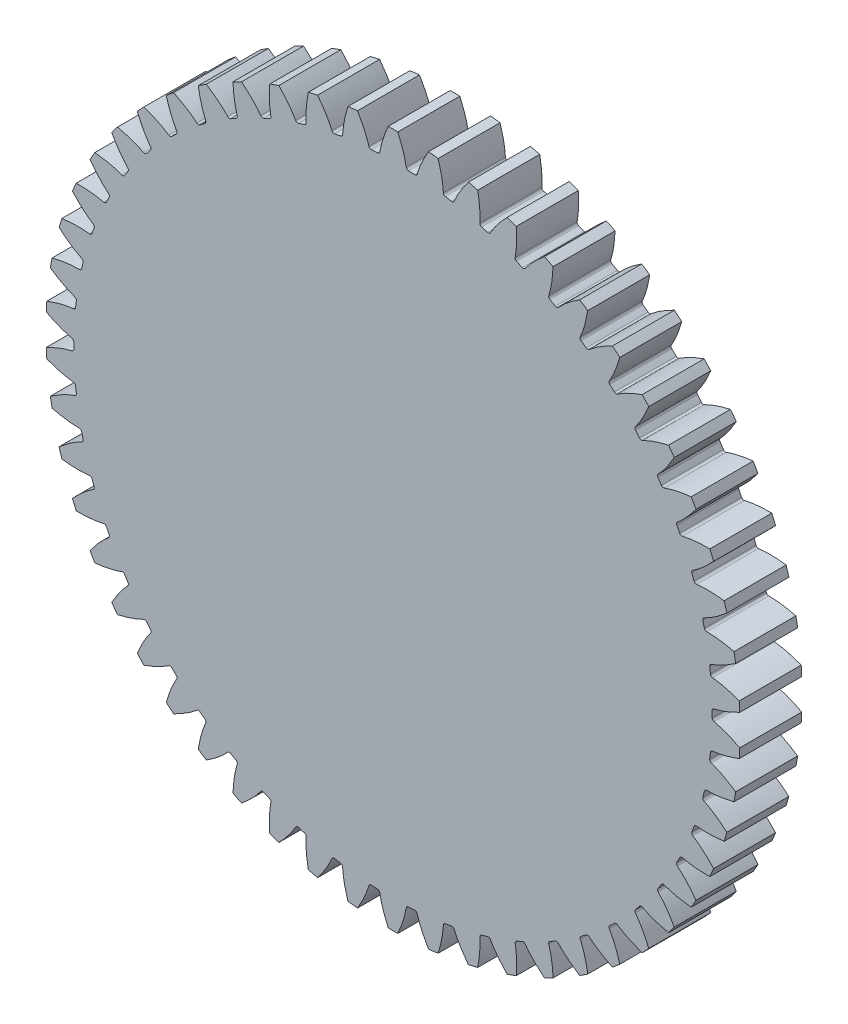
SolidWorks part; units mm, degrees
ref_plane "前视基准面" through (0, 0, 0) normal (0, 0, 1) x (1, 0, 0)
ref_plane "上视基准面" through (0, 0, 0) normal (0, 1, 0) x (1, 0, 0)
ref_plane "右视基准面" through (0, 0, 0) normal (1, 0, 0) x (0, 0, -1)
other "Configuration Table"
sketch "circles" plane through (0, 0, 0) normal (0, 0, 1) x (1, 0, 0)
  circle A0 centre (0, 0) radius 56000
  circle A1 centre (0, 0) radius 51500
  circle A2 centre (0, 0) radius 50743.4015
  circle A3 centre (0, 0) radius 54000
  dimension "D1" = 108000
  dimension "D2" = 101486.803
  dimension "D3" = 103000
  dimension "D4" = 112000
extrude "Gear_extrude" add sketch "circles" along normal blind 10000 contours A0
sketch "Involute" plane through (0, 0, 10000) normal (0, 0, 1) x (1, 0, 0)
  spline S0 degree 4 poles (50738.2969, -719.7424) (50738.6989, -719.7492) (50739.5031, -719.764) (50741.1112, -719.7997) (50743.5232, -719.8655) (50746.3369, -719.9491) (50750.356, -720.0854) (50755.1783, -720.2676) (50762.4104, -720.5706) (50772.0509, -721.0292) (50783.2948, -721.6297) (50796.1407, -722.393) (50812.1927, -723.4317) (50831.1111, -724.7774) (50852.8918, -726.4774) (50877.5298, -728.5801) (50901.8186, -730.8112) (50936.9721, -734.252) (50982.9627, -739.1667) (51043.9608, -746.3579) (51109.3546, -754.947) (51168.3219, -763.3206) (51234.9474, -773.3569) (51305.0207, -784.5405) (51393.4421, -799.6216) (51500.0905, -819.2298) (51613.1581, -841.4974) (51750.5558, -870.3767) (51876.7746, -898.8424) (52009.7781, -930.5506) (52182.9235, -974.0637) (52384.1424, -1027.6994) (52660.7454, -1107.2667) (52993.7639, -1211.7024) (53347.3188, -1331.9713) (53715.0055, -1466.8362) (54079.5977, -1609.7914) (54441.1235, -1760.3096) (54840.8093, -1936.0605) (55280.9542, -2141.1202) (55760.0369, -2378.2031) (56276.3509, -2650.0079) (56789.448, -2936.035) (57295.8631, -3233.7171) (57795.6354, -3542.4178) (58288.7943, -3861.5657) (58775.374, -4190.6497) (59255.4093, -4529.2084) (59728.9284, -4876.8157) (60195.9642, -5233.0852) (60656.5448, -5597.6556) (61110.7025, -5970.1966) (61558.4641, -6350.3958) (61999.8643, -6737.9683) (62434.9248, -7132.6363) (62863.6782, -7534.1477) (63286.1505, -7942.2588) (63702.3713, -8356.7431) (64112.3686, -8777.3843) (64516.1704, -9203.9774) (64916.8337, -9639.6208) (65409.1026, -10190.4255) (65986.8423, -10861.6333) (66642.4849, -11659.2604) (67364.4576, -12586.1414) (68062.5571, -13531.1238) (68736.9923, -14493.1316) (69387.9685, -15471.1592) (70015.6898, -16464.2658) (70620.3586, -17471.568) (71202.1764, -18492.2354) (71761.342, -19525.4818) (72298.0542, -20570.566) (72812.5079, -21626.7804) (73304.8974, -22693.4532) (73775.4183, -23769.9508) (74224.2605, -24855.659) (74651.6166, -25950.0005) (75057.677, -27052.4209) (75442.6292, -28162.3848) (75806.6612, -29279.3834) (76149.9593, -30402.927) (76472.7078, -31532.5421) (76775.0908, -32667.7749) (77057.2917, -33808.1917) (77319.492, -34953.3709) (77561.8726, -36102.9072) (77784.6129, -37256.408) (77987.8917, -38413.4962) (78171.8865, -39573.8054) (78336.7738, -40736.9815) (78482.7294, -41902.6839) (78625.8276, -43216.5679) (78757.7244, -44679.1708) (78869.1367, -46290.7564) (78936.4624, -47757.7842) (78969.4904, -48932.1208) (78982.0634, -49739.6722) (78985.8285, -50143.4774) (78987.2877, -50437.1606) (78987.6982, -50602.3592) (78987.801, -50712.4923) (78987.7729, -50804.2703) (78987.6822, -50877.6933) (78987.5234, -50951.116) (78987.2964, -51024.5388) (78987.0013, -51097.9609) (78986.6382, -51171.3835) (78986.207, -51244.8042) (78985.7079, -51318.2281) (78985.1409, -51391.6418) (78984.5057, -51465.0837) (78983.8916, -51529.2587) (78983.3198, -51584.5106) (78982.8215, -51630.0225) (78982.4003, -51666.9195) (78981.9549, -51704.3279) (78981.5114, -51740.2839) (78981.0625, -51775.5295) (78980.542, -51814.6197) (78979.9976, -51854.2012) (78979.5513, -51885.6417) (78978.9437, -51927.1306) (78978.3216, -51968.2967) (78977.7356, -52005.513) (78977.1081, -52044.3993) (78976.4454, -52084.2895) (78975.7794, -52123.1415) (78974.9176, -52172.0561) (78973.8455, -52230.7353) (78972.1654, -52318.7535) (78966.9801, -52573.022) (78955.0965, -53061.9596) (78924.9645, -54000.5264) (78858.8821, -55407.601) (78776.3299, -56637.4293) (78695.4859, -57612.2737) (78649.3376, -58118.8184) knots 0 0 0 0 0 0.000023 0.000047 0.000093 0.00014 0.000187 0.00028 0.000374 0.000561 0.000747 0.000934 0.001121 0.001495 0.001849 0.002203 0.002558 0.002912 0.003901 0.00489 0.006125 0.006743 0.00736 0.008804 0.010247 0.011953 0.013659 0.015497 0.018402 0.019468 0.021601 0.025867 0.030498 0.036186 0.041872 0.047558 0.053245 0.058932 0.064618 0.072918 0.081448 0.089978 0.098507 0.107037 0.115567 0.124097 0.132626 0.141156 0.149686 0.158216 0.166745 0.175275 0.183804 0.192334 0.200864 0.209394 0.217923 0.226453 0.234983 0.243513 0.252042 0.260832 0.277892 0.294951 0.312011 0.32907 0.346129 0.363189 0.380248 0.397308 0.414367 0.431427 0.448486 0.465546 0.482605 0.499664 0.516724 0.533783 0.550843 0.567902 0.584962 0.602021 0.61908 0.63614 0.653199 0.670259 0.687318 0.704378 0.721437 0.738496 0.755556 0.772615 0.789675 0.815264 0.840853 0.866442 0.874972 0.883502 0.887766 0.889899 0.892031 0.893098 0.894164 0.89523 0.896296 0.897362 0.898429 0.899495 0.900561 0.901627 0.902694 0.90376 0.904826 0.905359 0.905892 0.906425 0.906958 0.907492 0.908025 0.908558 0.909091 0.909659 0.910227 0.910795 0.911364 0.911932 0.9125 0.913068 0.913636 0.914773 0.915909 0.918182 0.928409 0.943182 0.970455 1 1 1 1 1 construction
  spline S2 degree 4 poles (50738.2969, 719.7424) (50738.6989, 719.7492) (50739.5031, 719.764) (50741.1112, 719.7997) (50743.5232, 719.8655) (50746.3369, 719.9491) (50750.356, 720.0854) (50755.1783, 720.2676) (50762.4104, 720.5706) (50772.0509, 721.0292) (50783.2948, 721.6297) (50796.1407, 722.393) (50812.1927, 723.4317) (50831.1111, 724.7774) (50852.8918, 726.4774) (50877.5298, 728.5801) (50901.8186, 730.8112) (50936.9721, 734.252) (50982.9627, 739.1667) (51043.9608, 746.3579) (51109.3546, 754.947) (51168.3219, 763.3206) (51234.9474, 773.3569) (51305.0207, 784.5405) (51393.4421, 799.6216) (51500.0905, 819.2298) (51613.1581, 841.4974) (51750.5558, 870.3767) (51876.7746, 898.8424) (52009.7781, 930.5506) (52182.9235, 974.0637) (52384.1424, 1027.6994) (52660.7454, 1107.2667) (52993.7639, 1211.7024) (53347.3188, 1331.9713) (53715.0055, 1466.8362) (54079.5977, 1609.7914) (54441.1235, 1760.3096) (54840.8093, 1936.0605) (55280.9542, 2141.1202) (55760.0369, 2378.2031) (56276.3509, 2650.0079) (56789.448, 2936.035) (57295.8631, 3233.7171) (57795.6354, 3542.4178) (58288.7943, 3861.5657) (58775.374, 4190.6497) (59255.4093, 4529.2084) (59728.9284, 4876.8157) (60195.9642, 5233.0852) (60656.5448, 5597.6556) (61110.7025, 5970.1966) (61558.4641, 6350.3958) (61999.8643, 6737.9683) (62434.9248, 7132.6363) (62863.6782, 7534.1477) (63286.1505, 7942.2588) (63702.3713, 8356.7431) (64112.3686, 8777.3843) (64516.1704, 9203.9774) (64916.8337, 9639.6208) (65409.1026, 10190.4255) (65986.8423, 10861.6333) (66642.4849, 11659.2604) (67364.4576, 12586.1414) (68062.5571, 13531.1238) (68736.9923, 14493.1316) (69387.9685, 15471.1592) (70015.6898, 16464.2658) (70620.3586, 17471.568) (71202.1764, 18492.2354) (71761.342, 19525.4818) (72298.0542, 20570.566) (72812.5079, 21626.7804) (73304.8974, 22693.4532) (73775.4183, 23769.9508) (74224.2605, 24855.659) (74651.6166, 25950.0005) (75057.677, 27052.4209) (75442.6292, 28162.3848) (75806.6612, 29279.3834) (76149.9593, 30402.927) (76472.7078, 31532.5421) (76775.0908, 32667.7749) (77057.2917, 33808.1917) (77319.492, 34953.3709) (77561.8726, 36102.9072) (77784.6129, 37256.408) (77987.8917, 38413.4962) (78171.8865, 39573.8054) (78336.7738, 40736.9815) (78482.7294, 41902.6839) (78625.8276, 43216.5679) (78757.7244, 44679.1708) (78869.1367, 46290.7564) (78936.4624, 47757.7842) (78969.4904, 48932.1208) (78982.0634, 49739.6722) (78985.8285, 50143.4774) (78987.2877, 50437.1606) (78987.6982, 50602.3592) (78987.801, 50712.4923) (78987.7729, 50804.2703) (78987.6822, 50877.6933) (78987.5234, 50951.116) (78987.2964, 51024.5388) (78987.0013, 51097.9609) (78986.6382, 51171.3835) (78986.207, 51244.8042) (78985.7079, 51318.2281) (78985.1409, 51391.6418) (78984.5057, 51465.0837) (78983.8916, 51529.2587) (78983.3198, 51584.5106) (78982.8215, 51630.0225) (78982.4003, 51666.9195) (78981.9549, 51704.3279) (78981.5114, 51740.2839) (78981.0625, 51775.5295) (78980.542, 51814.6197) (78979.9976, 51854.2012) (78979.5513, 51885.6417) (78978.9437, 51927.1306) (78978.3216, 51968.2967) (78977.7356, 52005.513) (78977.1081, 52044.3993) (78976.4454, 52084.2895) (78975.7794, 52123.1415) (78974.9176, 52172.0561) (78973.8455, 52230.7353) (78972.1654, 52318.7535) (78966.9801, 52573.022) (78955.0965, 53061.9596) (78924.9645, 54000.5264) (78858.8821, 55407.601) (78776.3299, 56637.4293) (78695.4859, 57612.2737) (78649.3376, 58118.8184) knots 0 0 0 0 0 0.000023 0.000047 0.000093 0.00014 0.000187 0.00028 0.000374 0.000561 0.000747 0.000934 0.001121 0.001495 0.001849 0.002203 0.002558 0.002912 0.003901 0.00489 0.006125 0.006743 0.00736 0.008804 0.010247 0.011953 0.013659 0.015497 0.018402 0.019468 0.021601 0.025867 0.030498 0.036186 0.041872 0.047558 0.053245 0.058932 0.064618 0.072918 0.081448 0.089978 0.098507 0.107037 0.115567 0.124097 0.132626 0.141156 0.149686 0.158216 0.166745 0.175275 0.183804 0.192334 0.200864 0.209394 0.217923 0.226453 0.234983 0.243513 0.252042 0.260832 0.277892 0.294951 0.312011 0.32907 0.346129 0.363189 0.380248 0.397308 0.414367 0.431427 0.448486 0.465546 0.482605 0.499664 0.516724 0.533783 0.550843 0.567902 0.584962 0.602021 0.61908 0.63614 0.653199 0.670259 0.687318 0.704378 0.721437 0.738496 0.755556 0.772615 0.789675 0.815264 0.840853 0.866442 0.874972 0.883502 0.887766 0.889899 0.892031 0.893098 0.894164 0.89523 0.896296 0.897362 0.898429 0.899495 0.900561 0.901627 0.902694 0.90376 0.904826 0.905359 0.905892 0.906425 0.906958 0.907492 0.908025 0.908558 0.909091 0.909659 0.910227 0.910795 0.911364 0.911932 0.9125 0.913068 0.913636 0.914773 0.915909 0.918182 0.928409 0.943182 0.970455 1 1 1 1 1 construction
  spline S3 degree 4 poles (50738.2969, 719.7424) (50738.6989, 719.7492) (50739.5031, 719.764) (50741.1112, 719.7997) (50743.5232, 719.8655) (50746.3369, 719.9491) (50750.356, 720.0854) (50755.1783, 720.2676) (50762.4104, 720.5706) (50772.0509, 721.0292) (50783.2948, 721.6297) (50796.1407, 722.393) (50812.1927, 723.4317) (50831.1111, 724.7774) (50852.8918, 726.4774) (50877.5298, 728.5801) (50901.8186, 730.8112) (50936.9721, 734.252) (50982.9627, 739.1667) (51043.9608, 746.3579) (51109.3546, 754.947) (51168.3219, 763.3206) (51234.9474, 773.3569) (51305.0207, 784.5405) (51393.4421, 799.6216) (51500.0905, 819.2298) (51613.1581, 841.4974) (51750.5558, 870.3767) (51876.7746, 898.8424) (52009.7781, 930.5506) (52182.9235, 974.0637) (52384.1424, 1027.6994) (52660.7454, 1107.2667) (52993.7639, 1211.7024) (53347.3188, 1331.9713) (53715.0055, 1466.8362) (54079.5977, 1609.7914) (54441.1235, 1760.3096) (54840.8093, 1936.0605) (55280.9542, 2141.1202) (55760.0369, 2378.2031) (56276.3509, 2650.0079) (56789.448, 2936.035) (57295.8631, 3233.7171) (57795.6354, 3542.4178) (58288.7943, 3861.5657) (58775.374, 4190.6497) (59255.4093, 4529.2084) (59728.9284, 4876.8157) (60195.9642, 5233.0852) (60656.5448, 5597.6556) (61110.7025, 5970.1966) (61558.4641, 6350.3958) (61999.8643, 6737.9683) (62434.9248, 7132.6363) (62863.6782, 7534.1477) (63286.1505, 7942.2588) (63702.3713, 8356.7431) (64112.3686, 8777.3843) (64516.1704, 9203.9774) (64916.8337, 9639.6208) (65409.1026, 10190.4255) (65986.8423, 10861.6333) (66642.4849, 11659.2604) (67364.4576, 12586.1414) (68062.5571, 13531.1238) (68736.9923, 14493.1316) (69387.9685, 15471.1592) (70015.6898, 16464.2658) (70620.3586, 17471.568) (71202.1764, 18492.2354) (71761.342, 19525.4818) (72298.0542, 20570.566) (72812.5079, 21626.7804) (73304.8974, 22693.4532) (73775.4183, 23769.9508) (74224.2605, 24855.659) (74651.6166, 25950.0005) (75057.677, 27052.4209) (75442.6292, 28162.3848) (75806.6612, 29279.3834) (76149.9593, 30402.927) (76472.7078, 31532.5421) (76775.0908, 32667.7749) (77057.2917, 33808.1917) (77319.492, 34953.3709) (77561.8726, 36102.9072) (77784.6129, 37256.408) (77987.8917, 38413.4962) (78171.8865, 39573.8054) (78336.7738, 40736.9815) (78482.7294, 41902.6839) (78625.8276, 43216.5679) (78757.7244, 44679.1708) (78869.1367, 46290.7564) (78936.4624, 47757.7842) (78969.4904, 48932.1208) (78982.0634, 49739.6722) (78985.8285, 50143.4774) (78987.2877, 50437.1606) (78987.6982, 50602.3592) (78987.801, 50712.4923) (78987.7729, 50804.2703) (78987.6822, 50877.6933) (78987.5234, 50951.116) (78987.2964, 51024.5388) (78987.0013, 51097.9609) (78986.6382, 51171.3835) (78986.207, 51244.8042) (78985.7079, 51318.2281) (78985.1409, 51391.6418) (78984.5057, 51465.0837) (78983.8916, 51529.2587) (78983.3198, 51584.5106) (78982.8215, 51630.0225) (78982.4003, 51666.9195) (78981.9549, 51704.3279) (78981.5114, 51740.2839) (78981.0625, 51775.5295) (78980.542, 51814.6197) (78980.1403, 51843.8255) (78979.9062, 51860.523) (78979.7879, 51868.8657) knots 0 0 0 0 0 0.000023 0.000047 0.000093 0.00014 0.000187 0.00028 0.000374 0.000561 0.000747 0.000934 0.001121 0.001495 0.001849 0.002203 0.002558 0.002912 0.003901 0.00489 0.006125 0.006743 0.00736 0.008804 0.010247 0.011953 0.013659 0.015497 0.018402 0.019468 0.021601 0.025867 0.030498 0.036186 0.041872 0.047558 0.053245 0.058932 0.064618 0.072918 0.081448 0.089978 0.098507 0.107037 0.115567 0.124097 0.132626 0.141156 0.149686 0.158216 0.166745 0.175275 0.183804 0.192334 0.200864 0.209394 0.217923 0.226453 0.234983 0.243513 0.252042 0.260832 0.277892 0.294951 0.312011 0.32907 0.346129 0.363189 0.380248 0.397308 0.414367 0.431427 0.448486 0.465546 0.482605 0.499664 0.516724 0.533783 0.550843 0.567902 0.584962 0.602021 0.61908 0.63614 0.653199 0.670259 0.687318 0.704378 0.721437 0.738496 0.755556 0.772615 0.789675 0.815264 0.840853 0.866442 0.874972 0.883502 0.887766 0.889899 0.892031 0.893098 0.894164 0.89523 0.896296 0.897362 0.898429 0.899495 0.900561 0.901627 0.902694 0.90376 0.904826 0.905359 0.905892 0.906425 0.906958 0.907492 0.908025 0.908558 0.909091 0.909091 0.909091 0.909091 0.909091
  spline S4 degree 4 poles (50738.2969, -719.7424) (50738.6989, -719.7492) (50739.5031, -719.764) (50741.1112, -719.7997) (50743.5232, -719.8655) (50746.3369, -719.9491) (50750.356, -720.0854) (50755.1783, -720.2676) (50762.4104, -720.5706) (50772.0509, -721.0292) (50783.2948, -721.6297) (50796.1407, -722.393) (50812.1927, -723.4317) (50831.1111, -724.7774) (50852.8918, -726.4774) (50877.5298, -728.5801) (50901.8186, -730.8112) (50936.9721, -734.252) (50982.9627, -739.1667) (51043.9608, -746.3579) (51109.3546, -754.947) (51168.3219, -763.3206) (51234.9474, -773.3569) (51305.0207, -784.5405) (51393.4421, -799.6216) (51500.0905, -819.2298) (51613.1581, -841.4974) (51750.5558, -870.3767) (51876.7746, -898.8424) (52009.7781, -930.5506) (52182.9235, -974.0637) (52384.1424, -1027.6994) (52660.7454, -1107.2667) (52993.7639, -1211.7024) (53347.3188, -1331.9713) (53715.0055, -1466.8362) (54079.5977, -1609.7914) (54441.1235, -1760.3096) (54840.8093, -1936.0605) (55280.9542, -2141.1202) (55760.0369, -2378.2031) (56276.3509, -2650.0079) (56789.448, -2936.035) (57295.8631, -3233.7171) (57795.6354, -3542.4178) (58288.7943, -3861.5657) (58775.374, -4190.6497) (59255.4093, -4529.2084) (59728.9284, -4876.8157) (60195.9642, -5233.0852) (60656.5448, -5597.6556) (61110.7025, -5970.1966) (61558.4641, -6350.3958) (61999.8643, -6737.9683) (62434.9248, -7132.6363) (62863.6782, -7534.1477) (63286.1505, -7942.2588) (63702.3713, -8356.7431) (64112.3686, -8777.3843) (64516.1704, -9203.9774) (64916.8337, -9639.6208) (65409.1026, -10190.4255) (65986.8423, -10861.6333) (66642.4849, -11659.2604) (67364.4576, -12586.1414) (68062.5571, -13531.1238) (68736.9923, -14493.1316) (69387.9685, -15471.1592) (70015.6898, -16464.2658) (70620.3586, -17471.568) (71202.1764, -18492.2354) (71761.342, -19525.4818) (72298.0542, -20570.566) (72812.5079, -21626.7804) (73304.8974, -22693.4532) (73775.4183, -23769.9508) (74224.2605, -24855.659) (74651.6166, -25950.0005) (75057.677, -27052.4209) (75442.6292, -28162.3848) (75806.6612, -29279.3834) (76149.9593, -30402.927) (76472.7078, -31532.5421) (76775.0908, -32667.7749) (77057.2917, -33808.1917) (77319.492, -34953.3709) (77561.8726, -36102.9072) (77784.6129, -37256.408) (77987.8917, -38413.4962) (78171.8865, -39573.8054) (78336.7738, -40736.9815) (78482.7294, -41902.6839) (78625.8276, -43216.5679) (78757.7244, -44679.1708) (78869.1367, -46290.7564) (78936.4624, -47757.7842) (78969.4904, -48932.1208) (78982.0634, -49739.6722) (78985.8285, -50143.4774) (78987.2877, -50437.1606) (78987.6982, -50602.3592) (78987.801, -50712.4923) (78987.7729, -50804.2703) (78987.6822, -50877.6933) (78987.5234, -50951.116) (78987.2964, -51024.5388) (78987.0013, -51097.9609) (78986.6382, -51171.3835) (78986.207, -51244.8042) (78985.7079, -51318.2281) (78985.1409, -51391.6418) (78984.5057, -51465.0837) (78983.8916, -51529.2587) (78983.3198, -51584.5106) (78982.8215, -51630.0225) (78982.4003, -51666.9195) (78981.9549, -51704.3279) (78981.5114, -51740.2839) (78981.0625, -51775.5295) (78980.542, -51814.6197) (78980.1403, -51843.8255) (78979.9062, -51860.523) (78979.7879, -51868.8657) knots 0 0 0 0 0 0.000023 0.000047 0.000093 0.00014 0.000187 0.00028 0.000374 0.000561 0.000747 0.000934 0.001121 0.001495 0.001849 0.002203 0.002558 0.002912 0.003901 0.00489 0.006125 0.006743 0.00736 0.008804 0.010247 0.011953 0.013659 0.015497 0.018402 0.019468 0.021601 0.025867 0.030498 0.036186 0.041872 0.047558 0.053245 0.058932 0.064618 0.072918 0.081448 0.089978 0.098507 0.107037 0.115567 0.124097 0.132626 0.141156 0.149686 0.158216 0.166745 0.175275 0.183804 0.192334 0.200864 0.209394 0.217923 0.226453 0.234983 0.243513 0.252042 0.260832 0.277892 0.294951 0.312011 0.32907 0.346129 0.363189 0.380248 0.397308 0.414367 0.431427 0.448486 0.465546 0.482605 0.499664 0.516724 0.533783 0.550843 0.567902 0.584962 0.602021 0.61908 0.63614 0.653199 0.670259 0.687318 0.704378 0.721437 0.738496 0.755556 0.772615 0.789675 0.815264 0.840853 0.866442 0.874972 0.883502 0.887766 0.889899 0.892031 0.893098 0.894164 0.89523 0.896296 0.897362 0.898429 0.899495 0.900561 0.901627 0.902694 0.90376 0.904826 0.905359 0.905892 0.906425 0.906958 0.907492 0.908025 0.908558 0.909091 0.909091 0.909091 0.909091 0.909091
sketch "Db>Df" [suppressed] plane through (0, 0, 10) normal (0, 0, 1) x (1, 0, 0)
  line L2 (0, 0) -> (29958.886, 1570.0787) construction
  line L3 (0, 0) -> (60247.7973, -1577.6441) construction
  line L4 (43195.2606, 29829.2216) -> (60247.7973, -1577.6441)
  line L5 (60247.7973, -1577.6441) -> (43195.2606, -29829.2216)
  circle A2 centre (0, 0) radius 30000 construction
  circle A3 centre (0, 0) radius 28190.7786 construction
  arc A4 (28171.0063, -1055.6527) -> (28171.0063, 1055.6527) centre (0, 0) ccw
  spline S0 degree 4 poles (28126.7994, -63.1481) (28109.5979, -1079.5949) (28131.6331, -1055.3685) (28153.5733, -1054.6775) (28176.2226, -1055.9127) (28179.03, -1056.0779) (28183.0394, -1056.3341) (28187.849, -1056.6667) (28193.4579, -1057.086) (28199.8653, -1057.6014) (28207.8712, -1058.2859) (28217.4732, -1059.1653) (28228.6684, -1060.2661) (28244.6499, -1061.9519) (28263.81, -1064.139) (28286.1383, -1066.9013) (28317.9947, -1071.1672) (28354.9201, -1076.5673) (28396.8859, -1083.2556) (28443.8595, -1091.3859) (28489.5039, -1099.8396) (28535.0535, -1108.7893) (28580.5096, -1118.2019) (28625.8732, -1128.05) (28671.1454, -1138.3103) (28736.3289, -1153.6788) (28821.2447, -1174.8864) (28925.648, -1202.8291) (29049.232, -1238.4977) (29182.732, -1279.6507) (29325.9529, -1326.7681) (29478.6839, -1380.3135) (29640.6983, -1440.7381) (29801.928, -1504.3161) (29962.3728, -1570.8924) (30122.0319, -1640.3333) (30280.904, -1712.5221) (30458.106, -1796.3967) (30653.1292, -1892.9155) (30865.4022, -2003.067) (31094.2933, -2127.8534) (31320.9217, -2257.2317) (31545.2947, -2390.9953) (31767.4188, -2528.9583) (31987.2997, -2670.9526) (32204.729, -2816.6746) (32419.7196, -2965.9728) (32685.4254, -3156.891) (32999.4431, -3392.6059) (33358.8036, -3676.7215) (33759.9986, -4013.0851) (34151.7765, -4360.3604) (34629.83, -4807.2635) (35184.9871, -5362.8299) (35957.4907, -6201.0931) (36762.6625, -7184.8659) (37513.0465, -8210.8377) (38209.8332, -9273.4633) (38750.2074, -10170.456) (39257.2317, -11086.6959) (39731.4078, -12020.34) (40173.2281, -12969.7103) (40583.1767, -13933.2591) (40961.73, -14909.559) (41309.357, -15897.2837) (41626.5204, -16895.1991) (41913.6764, -17902.1516) (42139.0755, -18790.1973) (42314.0797, -19555.7179) (42447.9237, -20196.2454) (42535.366, -20645.8749) (42629.3944, -21160.8429) (42716.3764, -21677.0558) (42796.3658, -22194.4054) (42877.2637, -22777.7459) (42942.3001, -23297.1773) (43000.5166, -23817.4172) (43051.9655, -24338.3698) (43096.699, -24859.9419) (43144.2864, -25512.5673) (43188.1677, -26296.5972) (43213.4164, -27016.0023) (43225.3967, -27735.7083) (43226.6775, -28259.1871) (43225.0232, -28553.6405) (43221.7166, -28815.3574) (43218.9961, -28978.9206) (43216.7492, -29093.4085) (43214.5791, -29191.536) (43212.6081, -29273.3049) (43210.9338, -29338.7179) (43209.1622, -29404.1279) (43207.2934, -29469.5359) (43205.3274, -29534.9397) (43203.5222, -29592.1679) (43201.9144, -29641.2138) (43200.5338, -29682.0963) (43199.4068, -29714.7541) (43198.3941, -29743.4765) (43197.5195, -29767.8649) (43195.5494, -29822.0864) (43192.8661, -29893.2843) (43197.3951, -29770.5374) (43157.721, -30826.3314) knots -0.00212 -0.00212 -0.00212 -0.00212 -0.00212 0.000042 0.000084 0.000168 0.000252 0.000336 0.000504 0.000672 0.00084 0.001008 0.001344 0.00168 0.002016 0.002688 0.00336 0.004033 0.005377 0.00659 0.007803 0.009017 0.01023 0.011444 0.012657 0.01387 0.015084 0.018446 0.021808 0.02517 0.028532 0.033051 0.037571 0.042091 0.04661 0.051171 0.055732 0.060294 0.064855 0.071669 0.078483 0.085297 0.092111 0.098952 0.105793 0.112635 0.119476 0.126318 0.133159 0.146842 0.160526 0.174209 0.187892 0.201575 0.228941 0.256307 0.307035 0.334401 0.361767 0.389134 0.4165 0.443866 0.471232 0.498598 0.525964 0.55333 0.580697 0.608063 0.635429 0.649112 0.662795 0.676478 0.68332 0.703844 0.717528 0.731211 0.744894 0.758577 0.77226 0.785943 0.799626 0.826992 0.854358 0.8612 0.874883 0.881725 0.885145 0.888566 0.891987 0.893697 0.895408 0.897118 0.898829 0.900539 0.902249 0.90396 0.904815 0.90567 0.906525 0.907381 0.907808 0.908236 0.912344 0.912344 0.912344 0.912344 0.912344 only from (28171.0063, -1055.6527) to (43195.2606, -29829.2216) construction
  spline S1 degree 4 poles (28126.7994, 63.1481) (28109.5979, 1079.5949) (28131.6331, 1055.3685) (28153.5733, 1054.6775) (28176.2226, 1055.9127) (28179.03, 1056.0779) (28183.0394, 1056.3341) (28187.849, 1056.6667) (28193.4579, 1057.086) (28199.8653, 1057.6014) (28207.8712, 1058.2859) (28217.4732, 1059.1653) (28228.6684, 1060.2661) (28244.6499, 1061.9519) (28263.81, 1064.139) (28286.1383, 1066.9013) (28317.9947, 1071.1672) (28354.9201, 1076.5673) (28396.8859, 1083.2556) (28443.8595, 1091.3859) (28489.5039, 1099.8396) (28535.0535, 1108.7893) (28580.5096, 1118.2019) (28625.8732, 1128.05) (28671.1454, 1138.3103) (28736.3289, 1153.6788) (28821.2447, 1174.8864) (28925.648, 1202.8291) (29049.232, 1238.4977) (29182.732, 1279.6507) (29325.9529, 1326.7681) (29478.6839, 1380.3135) (29640.6983, 1440.7381) (29801.928, 1504.3161) (29962.3728, 1570.8924) (30122.0319, 1640.3333) (30280.904, 1712.5221) (30458.106, 1796.3967) (30653.1292, 1892.9155) (30865.4022, 2003.067) (31094.2933, 2127.8534) (31320.9217, 2257.2317) (31545.2947, 2390.9953) (31767.4188, 2528.9583) (31987.2997, 2670.9526) (32204.729, 2816.6746) (32419.7196, 2965.9728) (32685.4254, 3156.891) (32999.4431, 3392.6059) (33358.8036, 3676.7215) (33759.9986, 4013.0851) (34151.7765, 4360.3604) (34629.83, 4807.2635) (35184.9871, 5362.8299) (35957.4907, 6201.0931) (36762.6625, 7184.8659) (37513.0465, 8210.8377) (38209.8332, 9273.4633) (38750.2074, 10170.456) (39257.2317, 11086.6959) (39731.4078, 12020.34) (40173.2281, 12969.7103) (40583.1767, 13933.2591) (40961.73, 14909.559) (41309.357, 15897.2837) (41626.5204, 16895.1991) (41913.6764, 17902.1516) (42139.0755, 18790.1973) (42314.0797, 19555.7179) (42447.9237, 20196.2454) (42535.366, 20645.8749) (42629.3944, 21160.8429) (42716.3764, 21677.0558) (42796.3658, 22194.4054) (42877.2637, 22777.7459) (42942.3001, 23297.1773) (43000.5166, 23817.4172) (43051.9655, 24338.3698) (43096.699, 24859.9419) (43144.2864, 25512.5673) (43188.1677, 26296.5972) (43213.4164, 27016.0023) (43225.3967, 27735.7083) (43226.6775, 28259.1871) (43225.0232, 28553.6405) (43221.7166, 28815.3574) (43218.9961, 28978.9206) (43216.7492, 29093.4085) (43214.5791, 29191.536) (43212.6081, 29273.3049) (43210.9338, 29338.7179) (43209.1622, 29404.1279) (43207.2934, 29469.5359) (43205.3274, 29534.9397) (43203.5222, 29592.1679) (43201.9144, 29641.2138) (43200.5338, 29682.0963) (43199.4068, 29714.7541) (43198.3941, 29743.4765) (43197.5195, 29767.8649) (43195.5494, 29822.0864) (43192.8661, 29893.2843) (43197.3951, 29770.5374) (43157.721, 30826.3314) knots -0.00212 -0.00212 -0.00212 -0.00212 -0.00212 0.000042 0.000084 0.000168 0.000252 0.000336 0.000504 0.000672 0.00084 0.001008 0.001344 0.00168 0.002016 0.002688 0.00336 0.004033 0.005377 0.00659 0.007803 0.009017 0.01023 0.011444 0.012657 0.01387 0.015084 0.018446 0.021808 0.02517 0.028532 0.033051 0.037571 0.042091 0.04661 0.051171 0.055732 0.060294 0.064855 0.071669 0.078483 0.085297 0.092111 0.098952 0.105793 0.112635 0.119476 0.126318 0.133159 0.146842 0.160526 0.174209 0.187892 0.201575 0.228941 0.256307 0.307035 0.334401 0.361767 0.389134 0.4165 0.443866 0.471232 0.498598 0.525964 0.55333 0.580697 0.608063 0.635429 0.649112 0.662795 0.676478 0.68332 0.703844 0.717528 0.731211 0.744894 0.758577 0.77226 0.785943 0.799626 0.826992 0.854358 0.8612 0.874883 0.881725 0.885145 0.888566 0.891987 0.893697 0.895408 0.897118 0.898829 0.900539 0.902249 0.90396 0.904815 0.90567 0.906525 0.907381 0.907808 0.908236 0.912344 0.912344 0.912344 0.912344 0.912344 only from (28171.0063, 1055.6527) to (43195.2606, 29829.2216) construction
  spline S2 degree 4 poles (28171.0063, -1055.6527) (28171.4077, -1055.6692) (28172.2105, -1055.7041) (28173.8156, -1055.7815) (28176.2226, -1055.9127) (28179.03, -1056.0779) (28183.0394, -1056.3341) (28187.849, -1056.6667) (28193.4579, -1057.086) (28199.8653, -1057.6014) (28207.8712, -1058.2859) (28217.4732, -1059.1653) (28228.6684, -1060.2661) (28244.6499, -1061.9519) (28263.81, -1064.139) (28286.1383, -1066.9013) (28317.9947, -1071.1672) (28354.9201, -1076.5673) (28396.8859, -1083.2556) (28443.8595, -1091.3859) (28489.5039, -1099.8396) (28535.0535, -1108.7893) (28580.5096, -1118.2019) (28625.8732, -1128.05) (28671.1454, -1138.3103) (28736.3289, -1153.6788) (28821.2447, -1174.8864) (28925.648, -1202.8291) (29049.232, -1238.4977) (29182.732, -1279.6507) (29325.9529, -1326.7681) (29478.6839, -1380.3135) (29640.6983, -1440.7381) (29801.928, -1504.3161) (29962.3728, -1570.8924) (30122.0319, -1640.3333) (30280.904, -1712.5221) (30458.106, -1796.3967) (30653.1292, -1892.9155) (30865.4022, -2003.067) (31094.2933, -2127.8534) (31320.9217, -2257.2317) (31545.2947, -2390.9953) (31767.4188, -2528.9583) (31987.2997, -2670.9526) (32204.729, -2816.6746) (32419.7196, -2965.9728) (32685.4254, -3156.891) (32999.4431, -3392.6059) (33358.8036, -3676.7215) (33759.9986, -4013.0851) (34151.7765, -4360.3604) (34629.83, -4807.2635) (35184.9871, -5362.8299) (35957.4907, -6201.0931) (36762.6625, -7184.8659) (37513.0465, -8210.8377) (38209.8332, -9273.4633) (38750.2074, -10170.456) (39257.2317, -11086.6959) (39731.4078, -12020.34) (40173.2281, -12969.7103) (40583.1767, -13933.2591) (40961.73, -14909.559) (41309.357, -15897.2837) (41626.5204, -16895.1991) (41913.6764, -17902.1516) (42139.0755, -18790.1973) (42314.0797, -19555.7179) (42447.9237, -20196.2454) (42535.366, -20645.8749) (42629.3944, -21160.8429) (42716.3764, -21677.0558) (42796.3658, -22194.4054) (42877.2637, -22777.7459) (42942.3001, -23297.1773) (43000.5166, -23817.4172) (43051.9655, -24338.3698) (43096.699, -24859.9419) (43144.2864, -25512.5673) (43188.1677, -26296.5972) (43213.4164, -27016.0023) (43225.3967, -27735.7083) (43226.6775, -28259.1871) (43225.0232, -28553.6405) (43221.7166, -28815.3574) (43218.9961, -28978.9206) (43216.7492, -29093.4085) (43214.5791, -29191.536) (43212.6081, -29273.3049) (43210.9338, -29338.7179) (43209.1622, -29404.1279) (43207.2934, -29469.5359) (43205.3274, -29534.9397) (43203.5222, -29592.1679) (43201.9144, -29641.2138) (43200.5338, -29682.0963) (43199.4068, -29714.7541) (43198.3941, -29743.4765) (43197.5195, -29767.8649) (43196.6509, -29791.7706) (43195.9528, -29810.6693) (43195.539, -29821.7911) (43195.2606, -29829.2216) knots 0 0 0 0 0 0.000042 0.000084 0.000168 0.000252 0.000336 0.000504 0.000672 0.00084 0.001008 0.001344 0.00168 0.002016 0.002688 0.00336 0.004033 0.005377 0.00659 0.007803 0.009017 0.01023 0.011444 0.012657 0.01387 0.015084 0.018446 0.021808 0.02517 0.028532 0.033051 0.037571 0.042091 0.04661 0.051171 0.055732 0.060294 0.064855 0.071669 0.078483 0.085297 0.092111 0.098952 0.105793 0.112635 0.119476 0.126318 0.133159 0.146842 0.160526 0.174209 0.187892 0.201575 0.228941 0.256307 0.307035 0.334401 0.361767 0.389134 0.4165 0.443866 0.471232 0.498598 0.525964 0.55333 0.580697 0.608063 0.635429 0.649112 0.662795 0.676478 0.68332 0.703844 0.717528 0.731211 0.744894 0.758577 0.77226 0.785943 0.799626 0.826992 0.854358 0.8612 0.874883 0.881725 0.885145 0.888566 0.891987 0.893697 0.895408 0.897118 0.898829 0.900539 0.902249 0.90396 0.904815 0.90567 0.906525 0.907381 0.907808 0.908236 0.909091 0.909091 0.909091 0.909091 0.909091
  spline S3 degree 4 poles (28171.0063, 1055.6527) (28171.4077, 1055.6692) (28172.2105, 1055.7041) (28173.8156, 1055.7815) (28176.2226, 1055.9127) (28179.03, 1056.0779) (28183.0394, 1056.3341) (28187.849, 1056.6667) (28193.4579, 1057.086) (28199.8653, 1057.6014) (28207.8712, 1058.2859) (28217.4732, 1059.1653) (28228.6684, 1060.2661) (28244.6499, 1061.9519) (28263.81, 1064.139) (28286.1383, 1066.9013) (28317.9947, 1071.1672) (28354.9201, 1076.5673) (28396.8859, 1083.2556) (28443.8595, 1091.3859) (28489.5039, 1099.8396) (28535.0535, 1108.7893) (28580.5096, 1118.2019) (28625.8732, 1128.05) (28671.1454, 1138.3103) (28736.3289, 1153.6788) (28821.2447, 1174.8864) (28925.648, 1202.8291) (29049.232, 1238.4977) (29182.732, 1279.6507) (29325.9529, 1326.7681) (29478.6839, 1380.3135) (29640.6983, 1440.7381) (29801.928, 1504.3161) (29962.3728, 1570.8924) (30122.0319, 1640.3333) (30280.904, 1712.5221) (30458.106, 1796.3967) (30653.1292, 1892.9155) (30865.4022, 2003.067) (31094.2933, 2127.8534) (31320.9217, 2257.2317) (31545.2947, 2390.9953) (31767.4188, 2528.9583) (31987.2997, 2670.9526) (32204.729, 2816.6746) (32419.7196, 2965.9728) (32685.4254, 3156.891) (32999.4431, 3392.6059) (33358.8036, 3676.7215) (33759.9986, 4013.0851) (34151.7765, 4360.3604) (34629.83, 4807.2635) (35184.9871, 5362.8299) (35957.4907, 6201.0931) (36762.6625, 7184.8659) (37513.0465, 8210.8377) (38209.8332, 9273.4633) (38750.2074, 10170.456) (39257.2317, 11086.6959) (39731.4078, 12020.34) (40173.2281, 12969.7103) (40583.1767, 13933.2591) (40961.73, 14909.559) (41309.357, 15897.2837) (41626.5204, 16895.1991) (41913.6764, 17902.1516) (42139.0755, 18790.1973) (42314.0797, 19555.7179) (42447.9237, 20196.2454) (42535.366, 20645.8749) (42629.3944, 21160.8429) (42716.3764, 21677.0558) (42796.3658, 22194.4054) (42877.2637, 22777.7459) (42942.3001, 23297.1773) (43000.5166, 23817.4172) (43051.9655, 24338.3698) (43096.699, 24859.9419) (43144.2864, 25512.5673) (43188.1677, 26296.5972) (43213.4164, 27016.0023) (43225.3967, 27735.7083) (43226.6775, 28259.1871) (43225.0232, 28553.6405) (43221.7166, 28815.3574) (43218.9961, 28978.9206) (43216.7492, 29093.4085) (43214.5791, 29191.536) (43212.6081, 29273.3049) (43210.9338, 29338.7179) (43209.1622, 29404.1279) (43207.2934, 29469.5359) (43205.3274, 29534.9397) (43203.5222, 29592.1679) (43201.9144, 29641.2138) (43200.5338, 29682.0963) (43199.4068, 29714.7541) (43198.3941, 29743.4765) (43197.5195, 29767.8649) (43196.6509, 29791.7706) (43195.9528, 29810.6693) (43195.539, 29821.7911) (43195.2606, 29829.2216) knots 0 0 0 0 0 0.000042 0.000084 0.000168 0.000252 0.000336 0.000504 0.000672 0.00084 0.001008 0.001344 0.00168 0.002016 0.002688 0.00336 0.004033 0.005377 0.00659 0.007803 0.009017 0.01023 0.011444 0.012657 0.01387 0.015084 0.018446 0.021808 0.02517 0.028532 0.033051 0.037571 0.042091 0.04661 0.051171 0.055732 0.060294 0.064855 0.071669 0.078483 0.085297 0.092111 0.098952 0.105793 0.112635 0.119476 0.126318 0.133159 0.146842 0.160526 0.174209 0.187892 0.201575 0.228941 0.256307 0.307035 0.334401 0.361767 0.389134 0.4165 0.443866 0.471232 0.498598 0.525964 0.55333 0.580697 0.608063 0.635429 0.649112 0.662795 0.676478 0.68332 0.703844 0.717528 0.731211 0.744894 0.758577 0.77226 0.785943 0.799626 0.826992 0.854358 0.8612 0.874883 0.881725 0.885145 0.888566 0.891987 0.893697 0.895408 0.897118 0.898829 0.900539 0.902249 0.90396 0.904815 0.90567 0.906525 0.907381 0.907808 0.908236 0.909091 0.909091 0.909091 0.909091 0.909091
  dimension "D1" = 4.5
  dimension "D2" = 60
extrude "extruded-cut1" [suppressed] cut sketch "Db>Df" against normal through all
fillet "fillet1" [suppressed] radius 380
pattern_circular "circular-parttern1" [suppressed] count 54 over 360 reverse direction yes of bodies 107
sketch "Db<Df" plane through (0, 0, 10000) normal (0, 0, 1) x (1, 0, 0)
  line L0 (0, 0) -> (108926.2914, 0) construction
  line L1 (0, 0) -> (53977.1553, 1570.5748) construction
  line L2 (78979.7879, 51868.8657) -> (108926.2914, 0)
  line L3 (108926.2914, 0) -> (78979.7879, -51868.8657)
  circle A0 centre (0, 0) radius 51500 construction
  arc A1 (51493.4988, -818.2784) -> (51493.4988, 818.2784) centre (0, 0) ccw
  circle A2 centre (0, 0) radius 54000 construction
  spline S0 degree 4 poles (50668.9349, -1256.9522) (50664.4511, 753.8781) (50690.3415, 720.5723) (50716.5544, 719.1299) (50743.5232, 719.8655) (50746.3369, 719.9491) (50750.356, 720.0854) (50755.1783, 720.2676) (50762.4104, 720.5706) (50772.0509, 721.0292) (50783.2948, 721.6297) (50796.1407, 722.393) (50812.1927, 723.4317) (50831.1111, 724.7774) (50852.8918, 726.4774) (50877.5298, 728.5801) (50901.8186, 730.8112) (50936.9721, 734.252) (50982.9627, 739.1667) (51043.9608, 746.3579) (51109.3546, 754.947) (51168.3219, 763.3206) (51234.9474, 773.3569) (51305.0207, 784.5405) (51393.4421, 799.6216) (51500.0905, 819.2298) (51613.1581, 841.4974) (51750.5558, 870.3767) (51876.7746, 898.8424) (52009.7781, 930.5506) (52182.9235, 974.0637) (52384.1424, 1027.6994) (52660.7454, 1107.2667) (52993.7639, 1211.7024) (53347.3188, 1331.9713) (53715.0055, 1466.8362) (54079.5977, 1609.7914) (54441.1235, 1760.3096) (54840.8093, 1936.0605) (55280.9542, 2141.1202) (55760.0369, 2378.2031) (56276.3509, 2650.0079) (56789.448, 2936.035) (57295.8631, 3233.7171) (57795.6354, 3542.4178) (58288.7943, 3861.5657) (58775.374, 4190.6497) (59255.4093, 4529.2084) (59728.9284, 4876.8157) (60195.9642, 5233.0852) (60656.5448, 5597.6556) (61110.7025, 5970.1966) (61558.4641, 6350.3958) (61999.8643, 6737.9683) (62434.9248, 7132.6363) (62863.6782, 7534.1477) (63286.1505, 7942.2588) (63702.3713, 8356.7431) (64112.3686, 8777.3843) (64516.1704, 9203.9774) (64916.8337, 9639.6208) (65409.1026, 10190.4255) (65986.8423, 10861.6333) (66642.4849, 11659.2604) (67364.4576, 12586.1414) (68062.5571, 13531.1238) (68736.9923, 14493.1316) (69387.9685, 15471.1592) (70015.6898, 16464.2658) (70620.3586, 17471.568) (71202.1764, 18492.2354) (71761.342, 19525.4818) (72298.0542, 20570.566) (72812.5079, 21626.7804) (73304.8974, 22693.4532) (73775.4183, 23769.9508) (74224.2605, 24855.659) (74651.6166, 25950.0005) (75057.677, 27052.4209) (75442.6292, 28162.3848) (75806.6612, 29279.3834) (76149.9593, 30402.927) (76472.7078, 31532.5421) (76775.0908, 32667.7749) (77057.2917, 33808.1917) (77319.492, 34953.3709) (77561.8726, 36102.9072) (77784.6129, 37256.408) (77987.8917, 38413.4962) (78171.8865, 39573.8054) (78336.7738, 40736.9815) (78482.7294, 41902.6839) (78625.8276, 43216.5679) (78757.7244, 44679.1708) (78869.1367, 46290.7564) (78936.4624, 47757.7842) (78969.4904, 48932.1208) (78982.0634, 49739.6722) (78985.8285, 50143.4774) (78987.2877, 50437.1606) (78987.6982, 50602.3592) (78987.801, 50712.4923) (78987.7729, 50804.2703) (78987.6822, 50877.6933) (78987.5234, 50951.116) (78987.2964, 51024.5388) (78987.0013, 51097.9609) (78986.6382, 51171.3835) (78986.207, 51244.8042) (78985.7079, 51318.2281) (78985.1409, 51391.6418) (78984.5057, 51465.0837) (78983.8916, 51529.2587) (78983.3198, 51584.5106) (78982.8215, 51630.0225) (78982.4003, 51666.9195) (78981.9549, 51704.3279) (78981.5114, 51740.2839) (78981.0625, 51775.5295) (78979.7753, 51872.1961) (78978.5189, 51958.108) (78979.7081, 51866.2722) (78951.1324, 53864.6012) knots -0.001427 -0.001427 -0.001427 -0.001427 -0.001427 0.000023 0.000047 0.000093 0.00014 0.000187 0.00028 0.000374 0.000561 0.000747 0.000934 0.001121 0.001495 0.001849 0.002203 0.002558 0.002912 0.003901 0.00489 0.006125 0.006743 0.00736 0.008804 0.010247 0.011953 0.013659 0.015497 0.018402 0.019468 0.021601 0.025867 0.030498 0.036186 0.041872 0.047558 0.053245 0.058932 0.064618 0.072918 0.081448 0.089978 0.098507 0.107037 0.115567 0.124097 0.132626 0.141156 0.149686 0.158216 0.166745 0.175275 0.183804 0.192334 0.200864 0.209394 0.217923 0.226453 0.234983 0.243513 0.252042 0.260832 0.277892 0.294951 0.312011 0.32907 0.346129 0.363189 0.380248 0.397308 0.414367 0.431427 0.448486 0.465546 0.482605 0.499664 0.516724 0.533783 0.550843 0.567902 0.584962 0.602021 0.61908 0.63614 0.653199 0.670259 0.687318 0.704378 0.721437 0.738496 0.755556 0.772615 0.789675 0.815264 0.840853 0.866442 0.874972 0.883502 0.887766 0.889899 0.892031 0.893098 0.894164 0.89523 0.896296 0.897362 0.898429 0.899495 0.900561 0.901627 0.902694 0.90376 0.904826 0.905359 0.905892 0.906425 0.906958 0.907492 0.908025 0.908558 0.912232 0.912232 0.912232 0.912232 0.912232 only from (50738.2969, 719.7424) to (78979.7879, 51868.8657) construction
  spline S1 degree 4 poles (51493.4988, 818.2784) (51508.4495, 821.1152) (51552.2357, 829.528) (51627.0079, 844.4085) (51750.5558, 870.3767) (51876.7746, 898.8424) (52009.7781, 930.5506) (52182.9235, 974.0637) (52384.1424, 1027.6994) (52660.7454, 1107.2667) (52993.7639, 1211.7024) (53347.3188, 1331.9713) (53715.0055, 1466.8362) (54079.5977, 1609.7914) (54441.1235, 1760.3096) (54840.8093, 1936.0605) (55280.9542, 2141.1202) (55760.0369, 2378.2031) (56276.3509, 2650.0079) (56789.448, 2936.035) (57295.8631, 3233.7171) (57795.6354, 3542.4178) (58288.7943, 3861.5657) (58775.374, 4190.6497) (59255.4093, 4529.2084) (59728.9284, 4876.8157) (60195.9642, 5233.0852) (60656.5448, 5597.6556) (61110.7025, 5970.1966) (61558.4641, 6350.3958) (61999.8643, 6737.9683) (62434.9248, 7132.6363) (62863.6782, 7534.1477) (63286.1505, 7942.2588) (63702.3713, 8356.7431) (64112.3686, 8777.3843) (64516.1704, 9203.9774) (64916.8337, 9639.6208) (65409.1026, 10190.4255) (65986.8423, 10861.6333) (66642.4849, 11659.2604) (67364.4576, 12586.1414) (68062.5571, 13531.1238) (68736.9923, 14493.1316) (69387.9685, 15471.1592) (70015.6898, 16464.2658) (70620.3586, 17471.568) (71202.1764, 18492.2354) (71761.342, 19525.4818) (72298.0542, 20570.566) (72812.5079, 21626.7804) (73304.8974, 22693.4532) (73775.4183, 23769.9508) (74224.2605, 24855.659) (74651.6166, 25950.0005) (75057.677, 27052.4209) (75442.6292, 28162.3848) (75806.6612, 29279.3834) (76149.9593, 30402.927) (76472.7078, 31532.5421) (76775.0908, 32667.7749) (77057.2917, 33808.1917) (77319.492, 34953.3709) (77561.8726, 36102.9072) (77784.6129, 37256.408) (77987.8917, 38413.4962) (78171.8865, 39573.8054) (78336.7738, 40736.9815) (78482.7294, 41902.6839) (78625.8276, 43216.5679) (78757.7244, 44679.1708) (78869.1367, 46290.7564) (78936.4624, 47757.7842) (78969.4904, 48932.1208) (78982.0634, 49739.6722) (78985.8285, 50143.4774) (78987.2877, 50437.1606) (78987.6982, 50602.3592) (78987.801, 50712.4923) (78987.7729, 50804.2703) (78987.6822, 50877.6933) (78987.5234, 50951.116) (78987.2964, 51024.5388) (78987.0013, 51097.9609) (78986.6382, 51171.3835) (78986.207, 51244.8042) (78985.7079, 51318.2281) (78985.1409, 51391.6418) (78984.5057, 51465.0837) (78983.8916, 51529.2587) (78983.3198, 51584.5106) (78982.8215, 51630.0225) (78982.4003, 51666.9195) (78981.9549, 51704.3279) (78981.5114, 51740.2839) (78981.0625, 51775.5295) (78980.542, 51814.6197) (78980.1403, 51843.8255) (78979.9062, 51860.523) (78979.7879, 51868.8657) knots 0.011069 0.011069 0.011069 0.011069 0.011069 0.011953 0.013659 0.015497 0.018402 0.019468 0.021601 0.025867 0.030498 0.036186 0.041872 0.047558 0.053245 0.058932 0.064618 0.072918 0.081448 0.089978 0.098507 0.107037 0.115567 0.124097 0.132626 0.141156 0.149686 0.158216 0.166745 0.175275 0.183804 0.192334 0.200864 0.209394 0.217923 0.226453 0.234983 0.243513 0.252042 0.260832 0.277892 0.294951 0.312011 0.32907 0.346129 0.363189 0.380248 0.397308 0.414367 0.431427 0.448486 0.465546 0.482605 0.499664 0.516724 0.533783 0.550843 0.567902 0.584962 0.602021 0.61908 0.63614 0.653199 0.670259 0.687318 0.704378 0.721437 0.738496 0.755556 0.772615 0.789675 0.815264 0.840853 0.866442 0.874972 0.883502 0.887766 0.889899 0.892031 0.893098 0.894164 0.89523 0.896296 0.897362 0.898429 0.899495 0.900561 0.901627 0.902694 0.90376 0.904826 0.905359 0.905892 0.906425 0.906958 0.907492 0.908025 0.908558 0.909091 0.909091 0.909091 0.909091 0.909091
  spline S2 degree 4 poles (50668.9349, 1256.9522) (50664.4511, -753.8781) (50690.3415, -720.5723) (50716.5544, -719.1299) (50743.5232, -719.8655) (50746.3369, -719.9491) (50750.356, -720.0854) (50755.1783, -720.2676) (50762.4104, -720.5706) (50772.0509, -721.0292) (50783.2948, -721.6297) (50796.1407, -722.393) (50812.1927, -723.4317) (50831.1111, -724.7774) (50852.8918, -726.4774) (50877.5298, -728.5801) (50901.8186, -730.8112) (50936.9721, -734.252) (50982.9627, -739.1667) (51043.9608, -746.3579) (51109.3546, -754.947) (51168.3219, -763.3206) (51234.9474, -773.3569) (51305.0207, -784.5405) (51393.4421, -799.6216) (51500.0905, -819.2298) (51613.1581, -841.4974) (51750.5558, -870.3767) (51876.7746, -898.8424) (52009.7781, -930.5506) (52182.9235, -974.0637) (52384.1424, -1027.6994) (52660.7454, -1107.2667) (52993.7639, -1211.7024) (53347.3188, -1331.9713) (53715.0055, -1466.8362) (54079.5977, -1609.7914) (54441.1235, -1760.3096) (54840.8093, -1936.0605) (55280.9542, -2141.1202) (55760.0369, -2378.2031) (56276.3509, -2650.0079) (56789.448, -2936.035) (57295.8631, -3233.7171) (57795.6354, -3542.4178) (58288.7943, -3861.5657) (58775.374, -4190.6497) (59255.4093, -4529.2084) (59728.9284, -4876.8157) (60195.9642, -5233.0852) (60656.5448, -5597.6556) (61110.7025, -5970.1966) (61558.4641, -6350.3958) (61999.8643, -6737.9683) (62434.9248, -7132.6363) (62863.6782, -7534.1477) (63286.1505, -7942.2588) (63702.3713, -8356.7431) (64112.3686, -8777.3843) (64516.1704, -9203.9774) (64916.8337, -9639.6208) (65409.1026, -10190.4255) (65986.8423, -10861.6333) (66642.4849, -11659.2604) (67364.4576, -12586.1414) (68062.5571, -13531.1238) (68736.9923, -14493.1316) (69387.9685, -15471.1592) (70015.6898, -16464.2658) (70620.3586, -17471.568) (71202.1764, -18492.2354) (71761.342, -19525.4818) (72298.0542, -20570.566) (72812.5079, -21626.7804) (73304.8974, -22693.4532) (73775.4183, -23769.9508) (74224.2605, -24855.659) (74651.6166, -25950.0005) (75057.677, -27052.4209) (75442.6292, -28162.3848) (75806.6612, -29279.3834) (76149.9593, -30402.927) (76472.7078, -31532.5421) (76775.0908, -32667.7749) (77057.2917, -33808.1917) (77319.492, -34953.3709) (77561.8726, -36102.9072) (77784.6129, -37256.408) (77987.8917, -38413.4962) (78171.8865, -39573.8054) (78336.7738, -40736.9815) (78482.7294, -41902.6839) (78625.8276, -43216.5679) (78757.7244, -44679.1708) (78869.1367, -46290.7564) (78936.4624, -47757.7842) (78969.4904, -48932.1208) (78982.0634, -49739.6722) (78985.8285, -50143.4774) (78987.2877, -50437.1606) (78987.6982, -50602.3592) (78987.801, -50712.4923) (78987.7729, -50804.2703) (78987.6822, -50877.6933) (78987.5234, -50951.116) (78987.2964, -51024.5388) (78987.0013, -51097.9609) (78986.6382, -51171.3835) (78986.207, -51244.8042) (78985.7079, -51318.2281) (78985.1409, -51391.6418) (78984.5057, -51465.0837) (78983.8916, -51529.2587) (78983.3198, -51584.5106) (78982.8215, -51630.0225) (78982.4003, -51666.9195) (78981.9549, -51704.3279) (78981.5114, -51740.2839) (78981.0625, -51775.5295) (78979.7753, -51872.1961) (78978.5189, -51958.108) (78979.7081, -51866.2722) (78951.1324, -53864.6012) knots -0.001427 -0.001427 -0.001427 -0.001427 -0.001427 0.000023 0.000047 0.000093 0.00014 0.000187 0.00028 0.000374 0.000561 0.000747 0.000934 0.001121 0.001495 0.001849 0.002203 0.002558 0.002912 0.003901 0.00489 0.006125 0.006743 0.00736 0.008804 0.010247 0.011953 0.013659 0.015497 0.018402 0.019468 0.021601 0.025867 0.030498 0.036186 0.041872 0.047558 0.053245 0.058932 0.064618 0.072918 0.081448 0.089978 0.098507 0.107037 0.115567 0.124097 0.132626 0.141156 0.149686 0.158216 0.166745 0.175275 0.183804 0.192334 0.200864 0.209394 0.217923 0.226453 0.234983 0.243513 0.252042 0.260832 0.277892 0.294951 0.312011 0.32907 0.346129 0.363189 0.380248 0.397308 0.414367 0.431427 0.448486 0.465546 0.482605 0.499664 0.516724 0.533783 0.550843 0.567902 0.584962 0.602021 0.61908 0.63614 0.653199 0.670259 0.687318 0.704378 0.721437 0.738496 0.755556 0.772615 0.789675 0.815264 0.840853 0.866442 0.874972 0.883502 0.887766 0.889899 0.892031 0.893098 0.894164 0.89523 0.896296 0.897362 0.898429 0.899495 0.900561 0.901627 0.902694 0.90376 0.904826 0.905359 0.905892 0.906425 0.906958 0.907492 0.908025 0.908558 0.912232 0.912232 0.912232 0.912232 0.912232 only from (50738.2969, -719.7424) to (78979.7879, -51868.8657) construction
  spline S3 degree 4 poles (51493.4988, -818.2784) (51508.4495, -821.1152) (51552.2357, -829.528) (51627.0079, -844.4085) (51750.5558, -870.3767) (51876.7746, -898.8424) (52009.7781, -930.5506) (52182.9235, -974.0637) (52384.1424, -1027.6994) (52660.7454, -1107.2667) (52993.7639, -1211.7024) (53347.3188, -1331.9713) (53715.0055, -1466.8362) (54079.5977, -1609.7914) (54441.1235, -1760.3096) (54840.8093, -1936.0605) (55280.9542, -2141.1202) (55760.0369, -2378.2031) (56276.3509, -2650.0079) (56789.448, -2936.035) (57295.8631, -3233.7171) (57795.6354, -3542.4178) (58288.7943, -3861.5657) (58775.374, -4190.6497) (59255.4093, -4529.2084) (59728.9284, -4876.8157) (60195.9642, -5233.0852) (60656.5448, -5597.6556) (61110.7025, -5970.1966) (61558.4641, -6350.3958) (61999.8643, -6737.9683) (62434.9248, -7132.6363) (62863.6782, -7534.1477) (63286.1505, -7942.2588) (63702.3713, -8356.7431) (64112.3686, -8777.3843) (64516.1704, -9203.9774) (64916.8337, -9639.6208) (65409.1026, -10190.4255) (65986.8423, -10861.6333) (66642.4849, -11659.2604) (67364.4576, -12586.1414) (68062.5571, -13531.1238) (68736.9923, -14493.1316) (69387.9685, -15471.1592) (70015.6898, -16464.2658) (70620.3586, -17471.568) (71202.1764, -18492.2354) (71761.342, -19525.4818) (72298.0542, -20570.566) (72812.5079, -21626.7804) (73304.8974, -22693.4532) (73775.4183, -23769.9508) (74224.2605, -24855.659) (74651.6166, -25950.0005) (75057.677, -27052.4209) (75442.6292, -28162.3848) (75806.6612, -29279.3834) (76149.9593, -30402.927) (76472.7078, -31532.5421) (76775.0908, -32667.7749) (77057.2917, -33808.1917) (77319.492, -34953.3709) (77561.8726, -36102.9072) (77784.6129, -37256.408) (77987.8917, -38413.4962) (78171.8865, -39573.8054) (78336.7738, -40736.9815) (78482.7294, -41902.6839) (78625.8276, -43216.5679) (78757.7244, -44679.1708) (78869.1367, -46290.7564) (78936.4624, -47757.7842) (78969.4904, -48932.1208) (78982.0634, -49739.6722) (78985.8285, -50143.4774) (78987.2877, -50437.1606) (78987.6982, -50602.3592) (78987.801, -50712.4923) (78987.7729, -50804.2703) (78987.6822, -50877.6933) (78987.5234, -50951.116) (78987.2964, -51024.5388) (78987.0013, -51097.9609) (78986.6382, -51171.3835) (78986.207, -51244.8042) (78985.7079, -51318.2281) (78985.1409, -51391.6418) (78984.5057, -51465.0837) (78983.8916, -51529.2587) (78983.3198, -51584.5106) (78982.8215, -51630.0225) (78982.4003, -51666.9195) (78981.9549, -51704.3279) (78981.5114, -51740.2839) (78981.0625, -51775.5295) (78980.542, -51814.6197) (78980.1403, -51843.8255) (78979.9062, -51860.523) (78979.7879, -51868.8657) knots 0.011069 0.011069 0.011069 0.011069 0.011069 0.011953 0.013659 0.015497 0.018402 0.019468 0.021601 0.025867 0.030498 0.036186 0.041872 0.047558 0.053245 0.058932 0.064618 0.072918 0.081448 0.089978 0.098507 0.107037 0.115567 0.124097 0.132626 0.141156 0.149686 0.158216 0.166745 0.175275 0.183804 0.192334 0.200864 0.209394 0.217923 0.226453 0.234983 0.243513 0.252042 0.260832 0.277892 0.294951 0.312011 0.32907 0.346129 0.363189 0.380248 0.397308 0.414367 0.431427 0.448486 0.465546 0.482605 0.499664 0.516724 0.533783 0.550843 0.567902 0.584962 0.602021 0.61908 0.63614 0.653199 0.670259 0.687318 0.704378 0.721437 0.738496 0.755556 0.772615 0.789675 0.815264 0.840853 0.866442 0.874972 0.883502 0.887766 0.889899 0.892031 0.893098 0.894164 0.89523 0.896296 0.897362 0.898429 0.899495 0.900561 0.901627 0.902694 0.90376 0.904826 0.905359 0.905892 0.906425 0.906958 0.907492 0.908025 0.908558 0.909091 0.909091 0.909091 0.909091 0.909091
  dimension "D1" = 1.667
  dimension "D2" = 60
extrude "extruded-cut2" cut sketch "Db<Df" against normal through all
fillet "fillet2" radius 380 2 edges at (51493.4988, -818.2784, 5000) (51493.4988, 818.2784, 5000)
pattern_circular "circular-parttern2" count 54 over 360 about axis through (0, 0, 10000) along (0, 0, -1) of "extruded-cut2", "fillet2"
sketch3d "3DSketch1"
  line L0 (0, 0, 0) -> (0, 0, 10) construction
ref_axis "central_axis" through (0, 0, 0) along (0, 0, 1)
ref_plane "mounting_face" through (0, 0, 0) normal (0, 0, 1) x (1, 0, 0)
sketch3d "3DSketch2"
  line L0 (0, 0, 0) -> (0, 0, 1) construction
ref_axis "center_point" through (0, 0, 0) along (0, 0, 1)
equation "\"M\" = 2.0"
equation "\"Z\" = 54"
equation "\"B\" = 10.0"
equation "\"Alpha\"= 20\t'压力角"
equation "\"D\"= \"M\"*\"Z\"   '分度圆"
equation "\"Db\"= \"D\" * cos ( \"Alpha\" )  \t'基圆"
equation "\"Hax\"= 1'齿顶高系数"
equation "\"Cx\"= 0.25\t'顶隙系数"
equation "\"Ha\"= \"Hax\" * \"M\"\t'齿顶高"
equation "\"Hf\"= ( \"Hax\" + \"Cx\" ) * \"M\"\t'齿根高"
equation "\"Df\"= \"D\" - 2 * \"Hf\"\t\t'齿根圆"
equation "\"Da\"= \"D\" + 2 * \"Ha\"\t'齿顶圆"
equation "\"Theta\"= 360 * sqr ( ( 1 / cos ( \"Alpha\" ) ) ^ 2 - 1 ) / ( 2 * pi ) - atn ( sqr ( ( 1 / cos ( \"Alpha\" ) ) ^ 2 - 1 ) )"
equation "\"Phi\"= - ( 2 * pi * ( 90 / \"Z\" - \"Theta\" ) / 360 )"
equation "\"D1@circles\" = \"D\""
equation "\"D2@circles\" = \"Db\""
equation "\"D3@circles\" = \"Df\""
equation "\"D4@circles\" = \"Da\""
equation "\"D1@Gear_extrude\" = \"B\""
equation "\"D1@circular-parttern1\" = \"Z\""
equation "\"Db>Df\"= IIF ( \"Db\" > \"Df\" ,  unsuppressed  ,  suppressed  ) "
equation "\"extruded-cut1\"= IIF ( \"Db\" > \"Df\" ,  unsuppressed  ,  suppressed  ) "
equation "\"D1@Db<Df\"=90/\"Z\""
equation "\"D1@fillet1\" = 0.19 * \"M\""
equation "\"Db<Df\" = IIF ( \"Db\" < \"Df\" , \"unsuppressed\" , \"suppressed\" )"
equation "\"extruded-cut2\"= IIF ( \"Db\" < \"Df\" ,  unsuppressed  ,  suppressed  ) "
equation "\"D1@fillet2\" = 0.19 * \"M\""
equation "\"D1@circular-parttern2\" = \"Z\""
equation "\"circular-parttern2\"= IIF ( \"Db\" < \"Df\" ,  unsuppressed  ,  suppressed  ) "
equation "\"fillet1\"= IIF ( \"Db\" > \"Df\" ,  unsuppressed  ,  suppressed  ) "
equation "\"fillet2\"= IIF ( \"Db\" < \"Df\" ,  unsuppressed  ,  suppressed  ) "
equation "\"circular-parttern1\"= IIF ( \"Db\" > \"Df\" , \"unsuppressed\" , \"suppressed\" )"
